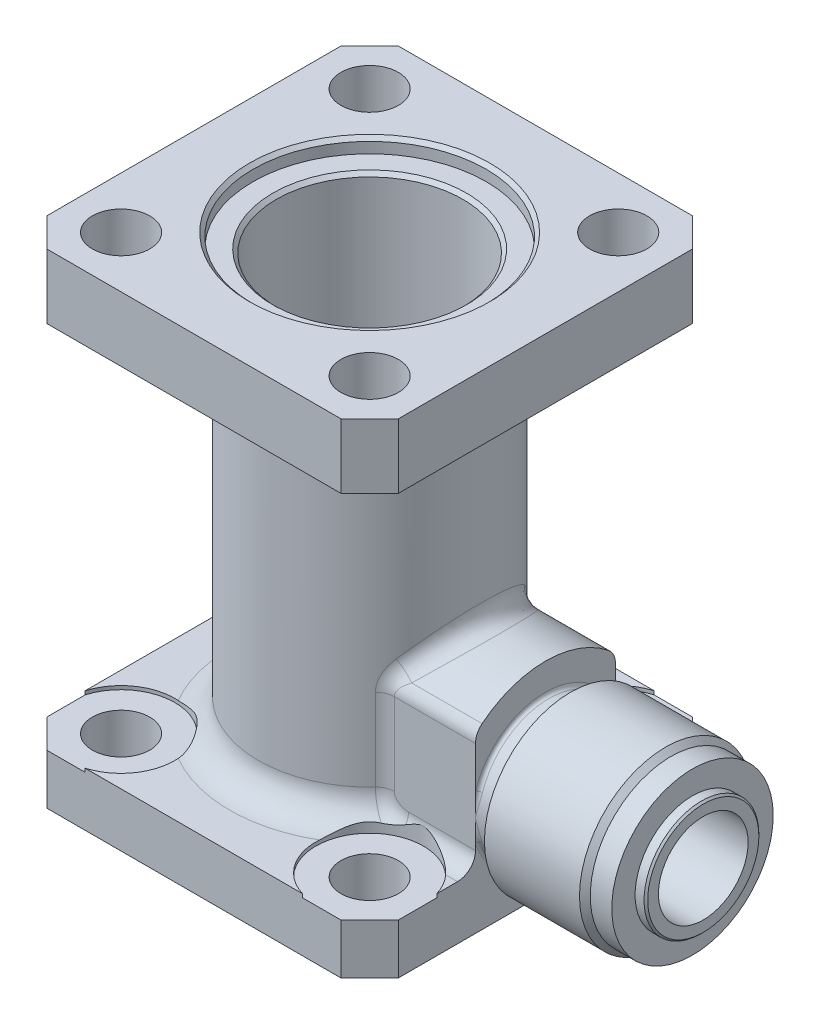
SolidWorks part; units mm, degrees
note: The reader was unsure of these and kept them because the rebuilt part matched: shared geometry of "Эскиз1<3>", "Эскиз3<3>".
material "08Х18Н10Т ГОСТ 5632-72"
ref_plane "Спереди" through (0, 0, 0) normal (0, 0, 1) x (1, 0, 0)
ref_plane "Сверху" through (0, 0, 0) normal (0, 1, 0) x (1, 0, 0)
ref_plane "Справа" through (0, 0, 0) normal (1, 0, 0) x (0, 0, -1)
sketch "Эскиз1" plane through (0, 0, 0) normal (0, 0, 1) x (1, 0, 0)
  line L0 (0, 124.0118) -> (0, -119.2051) construction
  line L1 (-125.9345, 0) -> (116.8018, 0) construction
  line L2 (-37.5, 107) -> (-33.5, 107)
  line L3 (-33.5, 107) -> (-32.5, 106)
  line L4 (-32.5, 106) -> (-32.5, 103)
  line L5 (-32.5, 103) -> (-27, 103)
  line L6 (-27, 103) -> (-26, 102)
  line L7 (-26, 102) -> (-26, 22)
  line L8 (-37.5, 107) -> (-37.5, 89)
  line L9 (-35.6667, 89) -> (-37.5, 89)
  line L11 (-35.6667, 89) -> (-31.2566, 75.7698)
  line L12 (-31, 74.1886) -> (-31, -5)
  line L13 (-31, 75) -> (-31, 78) construction
  line L14 (-31, 78) -> (-32, 78) construction
  line L15 (-39, -13) -> (-49, -13)
  line L16 (-49, -13) -> (-49, -28)
  line L17 (-49, -28) -> (-36, -28)
  line L18 (-36, -28) -> (-36, -36)
  line L19 (-36, -36) -> (-30, -36)
  line L20 (-30, -36) -> (-30, -41)
  line L21 (-30, -41) -> (-28, -41)
  line L22 (-28, -41) -> (-28, -17)
  line L23 (-28, -17) -> (-20, -17)
  line L24 (-20, -17) -> (-20, -19)
  line L25 (-20, -19) -> (-16.5, -19)
  line L26 (-13.5, -16) -> (-13.5, 14)
  line L27 (-25, 21) -> (0, 21)
  line L28 (0, 21) -> (0, 14)
  line L29 (0, 14) -> (-13.5, 14)
  line L30 (-33.5, 107) -> (0, 107)
  line L31 (0, 107) -> (0, 21)
  line L32 (-28, -41) -> (0, -41)
  line L33 (0, -41) -> (0, 14)
  arc A0 (-31, -5) -> (-39, -13) centre (-39, -5) cw
  arc A1 (-26, 22) -> (-25, 21) centre (-25, 22) ccw
  arc A2 (-31.2566, 75.7698) -> (-31, 74.1886) centre (-36, 74.1886) cw
  arc A3 (-16.5, -19) -> (-13.5, -16) centre (-16.5, -16) ccw
  dimension "D12" = 8
  dimension "D28" = 1
  dimension "D31" = 5
  dimension "D27" = 3
  dimension "D1" = 45
  dimension "D2" = 1
  dimension "D3" = 65
  dimension "D4" = 52
  dimension "D5" = 4
  dimension "D6" = 75
  dimension "D7" = 18
  dimension "D8" = 62
  dimension "D10" = 3
  dimension "D11" = 1
  dimension "D13" = 27
  dimension "D14" = 40
  dimension "D15" = 2
  dimension "D16" = 5
  dimension "D17" = 13
  dimension "D18" = 15
  dimension "D19" = 88
  dimension "D20" = 148
  dimension "D21" = 22
  dimension "D22" = 28
  dimension "D23" = 60
  dimension "D24" = 56
  dimension "D25" = 72
  dimension "D26" = 98
  dimension "D29" = 86
  dimension "D30" = 55
revolve "Повернуть1" add sketch "Эскиз1" angle 360 about L0
sketch "Эскиз2" plane through (0, -13, 0) normal (0, 1, 0) x (1, 0, 0)
  line L0 (-49, -41) -> (-41, -49)
  line L1 (-41, 49) -> (41, 49)
  line L2 (-49, 41) -> (-49, -41)
  line L3 (-41, -49) -> (41, -49)
  line L4 (49, 41) -> (49, -41)
  line L5 (-49, 49) -> (49, -49) construction
  line L6 (-49, -49) -> (49, 49) construction
  line L7 (41, -49) -> (49, -41)
  line L8 (41, 49) -> (49, 41)
  line L9 (-49, 41) -> (-41, 49)
  circle A0 centre (0, 0) radius 49 construction
  point P0 (0, 0)
  dimension "D1" = 8
  dimension "D2" = 8
  dimension "D3" = 8
  dimension "D4" = 8
  dimension "D5" = 8
  dimension "D6" = 8
  dimension "D7" = 8
  dimension "D8" = 8
extrude "Бобышка-Вытянуть1" add sketch "Эскиз2" against normal up to surface (15 mm away) up to face at (-36, -28, 0)
sketch "Эскиз3" plane through (0, 0, 0) normal (0, 0, 1) x (1, 0, 0)
  line L0 (116.8018, 0) -> (0, 0) construction
  line L1 (0, 0) -> (0, 19.5)
  line L2 (0, 19.5) -> (52.9116, 19.5)
  line L3 (53.7858, 20.0144) -> (56, 24)
  line L4 (56, 24) -> (82.5, 24)
  line L5 (82.5, 24) -> (84, 22.5)
  line L6 (84, 22.5) -> (90, 22.5)
  line L7 (90, 22.5) -> (90, 16)
  line L8 (90, 16) -> (92.5, 16)
  line L9 (93, 15.5) -> (93, 12.5)
  line L10 (92.5, 16) -> (93, 15.5)
  line L11 (93, 12.5) -> (0, 12.5)
  line L12 (93, 12.5) -> (93, 0)
  line L13 (93, 0) -> (0, 0)
  line L14 (49, -28) -> (49, -13) construction
  arc A0 (52.9116, 19.5) -> (53.7858, 20.0144) centre (52.9116, 20.5) ccw
  point P12 (93, 16)
  point P19 (53.5, 19.5)
  dimension "D6" = 1
  dimension "D1" = 0.5
  dimension "D2" = 45
  dimension "D3" = 3
  dimension "D4" = 6
  dimension "D5" = 45
  dimension "D7" = 4.5
  dimension "D8" = 7
  dimension "D9" = 48
  dimension "D10" = 39
  dimension "D11" = 25
  dimension "D12" = 45
  dimension "D13" = 32
  dimension "D14" = 93
revolve "Повернуть2" add sketch "Эскиз3" angle 360 about L0
cosmetic thread "Условное изображение резьбы1" parameters "D2"=46
sketch "Эскиз6" plane through (49, 0, 0) normal (1, 0, 0) x (0, 0, -1)
  line L0 (-41, -13) -> (-14.5344, -13) construction
  line L1 (-19.5, -13) -> (19.5, -13)
  line L2 (-19.5, -13) -> (-19.5, 17.8536)
  line L4 (19.5, -13) -> (19.5, 17.8536)
  arc A0 (-17.6522, 21.7348) -> (17.6522, 21.7348) centre (0, 0) cw
  arc A2 (17.6522, 21.7348) -> (19.5, 17.8536) centre (14.5, 17.8536) cw
  arc A3 (-19.5, 17.8536) -> (-17.6522, 21.7348) centre (-14.5, 17.8536) cw
  point P6 (0, -13)
  dimension "D2" = 28
  dimension "D3" = 5
  dimension "D1" = 39
extrude "Бобышка-Вытянуть3" add sketch "Эскиз6" against normal up to next
fillet "Скругление1" radius 5 9 edges at (41.3875, -13, -19.5) (39.8438, 0.9392, -19.5) (24.0988, 6.4268, -19.5) (24.6881, 20.4904, -18.7482) (30.9108, 27.9012, 2.3501) (24.6928, 20.5002, 18.7421) (24.0988, 6.4268, 19.5) (40.478, 0.3696, 19.5) (41.3875, -13, 19.5)
fillet "Скругление2" radius 1 2 edges at (49, 19.5, 0) (49, -19.5, 0)
revolve "Вырез-Повернуть1" cut sketch "Эскиз1<3>" angle 360 about L0
sketch "Эскиз1<3>" plane through (0, 0, 0) normal (0, 0, 1) x (1, 0, 0) same geometry as "Эскиз1"
revolve "Вырез-Повернуть2" cut sketch "Эскиз3<3>" angle 360 about L0
sketch "Эскиз3<3>" plane through (0, 0, 0) normal (0, 0, 1) x (1, 0, 0) same geometry as "Эскиз3"
sketch "Эскиз7" plane through (0, 21, 0) normal (0, 1, 0) x (1, 0, 0)
  line L0 (7.25, 5) -> (-0.25, 5)
  line L1 (7.25, -5) -> (-0.25, -5)
  arc A0 (-0.25, 5) -> (-0.25, -5) centre (-5.5, 0) ccw
  arc A1 (7.25, -5) -> (7.25, 5) centre (7.25, 0) ccw
  dimension "D1" = 14.5
  dimension "D2" = 5
  dimension "D3" = 25
  dimension "D4" = 5.5
extrude "Вырез-Вытянуть1" cut sketch "Эскиз7" against normal through all
sketch "Эскиз9" plane through (0, -13, 0) normal (0, 1, 0) x (1, 0, 0)
  line L0 (-34.6482, -34.6482) -> (0, 0) construction
  line L1 (0, 0) -> (0, -49) construction
  circle A0 centre (-34.6482, -34.6482) radius 8
  circle A1 centre (0, 0) radius 49 construction
  dimension "D2" = 98
  dimension "D3" = 16
  dimension "D1" = 45
extrude "Вырез-Вытянуть3" cut sketch "Эскиз9" against normal through all
sketch "Эскиз10" plane through (0, -13, 0) normal (0, 1, 0) x (1, 0, 0)
  line L0 (-49, 41) -> (-49, -41) construction
  line L1 (-49, -41) -> (-41, -49) construction
  line L2 (-41, -49) -> (41, -49) construction
  line L3 (-49, -30.2863) -> (-49, -41)
  line L4 (-49, -41) -> (-41, -49)
  line L5 (-41, -49) -> (-30.2863, -49)
  arc A0 (-30.2863, -49) -> (-49, -30.2863) centre (-34.6482, -34.6482) ccw
  dimension "D1" = 30
extrude "Вырез-Вытянуть4" cut sketch "Эскиз10" against normal blind 1 and the other way blind 10
pattern_circular "Круговой массив2" count 4 over 360 about axis through (0, 0, 0) along (0, 1, 0) of "Вырез-Вытянуть3", "Вырез-Вытянуть4"
sketch "Эскиз11" plane through (0, 107, 0) normal (0, 1, 0) x (1, 0, 0)
  line L8 (-49, -41) -> (-41, -49)
  line L9 (-41, -49) -> (41, -49)
  line L10 (41, -49) -> (49, -41)
  line L11 (49, -41) -> (49, 41)
  line L12 (49, 41) -> (41, 49)
  line L13 (41, 49) -> (-41, 49)
  line L14 (-41, 49) -> (-49, 41)
  line L15 (-49, 41) -> (-49, -41)
  line L16 (-49, -41) -> (-41, -49)
  line L17 (-41, -49) -> (41, -49)
  line L18 (41, -49) -> (49, -41)
  line L19 (49, -41) -> (49, 41)
  line L20 (49, 41) -> (41, 49)
  line L21 (41, 49) -> (-41, 49)
  line L22 (-41, 49) -> (-49, 41)
  line L23 (-49, 41) -> (-49, -41)
  circle A0 centre (-34.6482, 34.6482) radius 8 construction
  circle A1 centre (34.6482, 34.6482) radius 8 construction
  circle A2 centre (-34.6482, -34.6482) radius 8 construction
  circle A3 centre (34.6482, -34.6482) radius 8 construction
  circle A4 centre (-34.6482, 34.6482) radius 8
  circle A5 centre (34.6482, 34.6482) radius 8
  circle A6 centre (-34.6482, -34.6482) radius 8
  circle A7 centre (34.6482, -34.6482) radius 8
  circle A8 centre (0, 0) radius 37.5 construction
  circle A9 centre (0, 0) radius 37.5
  dimension "D1" = 0
extrude "Бобышка-Вытянуть4" add sketch "Эскиз11" against normal up to surface (18 mm away) up to face at (-37.5, 89, 0)
